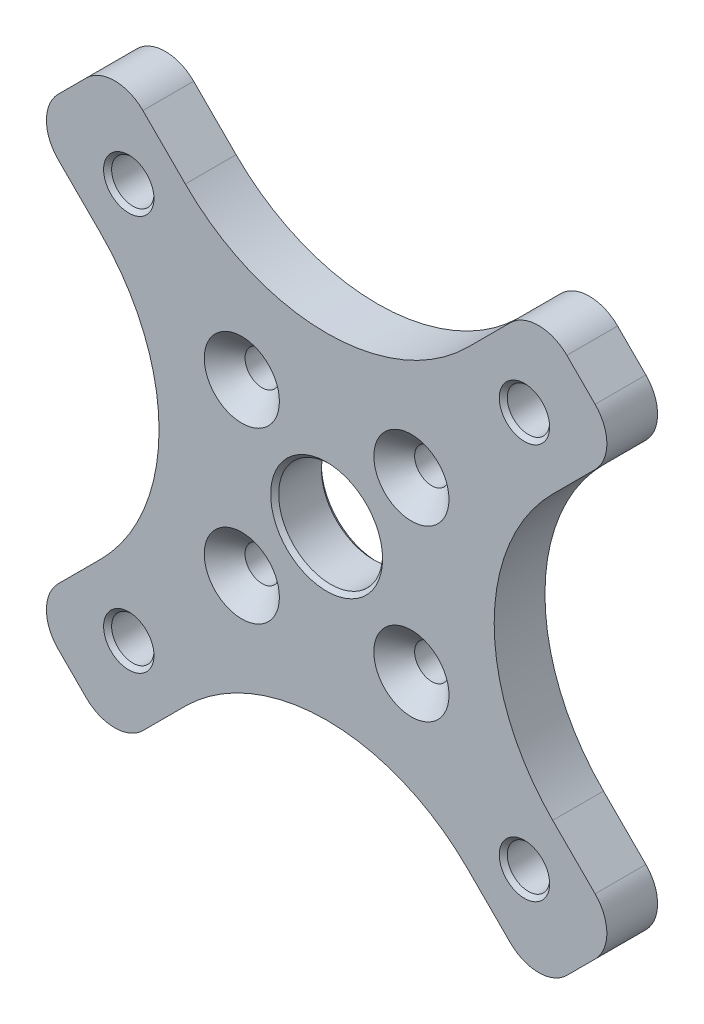
SolidWorks part; units mm, degrees
ref_plane "Front Plane" through (0, 0, 0) normal (0, 0, 1) x (1, 0, 0)
ref_plane "Top Plane" through (0, 0, 0) normal (0, 1, 0) x (1, 0, 0)
ref_plane "Right Plane" through (0, 0, 0) normal (1, 0, 0) x (0, 0, -1)
sketch "Sketch1" plane through (0, 0, 0) normal (0, 0, 1) x (1, 0, 0)
  line L0 (0, 10.6066) -> (26.5165, 37.1231)
  line L1 (26.5165, 37.1231) -> (37.1231, 26.5165)
  line L2 (37.1231, 26.5165) -> (10.6066, 0)
  line L3 (10.6066, 0) -> (37.1231, -26.5165)
  line L4 (37.1231, -26.5165) -> (26.5165, -37.1231)
  line L5 (26.5165, -37.1231) -> (0, -10.6066)
  line L6 (0, -10.6066) -> (-26.5165, -37.1231)
  line L7 (-26.5165, -37.1231) -> (-37.1231, -26.5165)
  line L8 (-37.1231, -26.5165) -> (-10.6066, 0)
  line L9 (-10.6066, 0) -> (-37.1231, 26.5165)
  line L10 (-37.1231, 26.5165) -> (-26.5165, 37.1231)
  line L11 (-26.5165, 37.1231) -> (0, 10.6066)
  line L12 (-31.8198, -31.8198) -> (31.8198, 31.8198) construction
  line L13 (-31.8198, 31.8198) -> (31.8198, -31.8198) construction
  line L14 (0, 0) -> (58.3953, 0) construction
  circle A0 centre (0, 0) radius 6.5
  dimension "D1" = 13
  dimension "D5" = 63.6396
  dimension "D2" = 45
  dimension "D3" = 15
  dimension "D4" = 90
extrude "1/4 in Sheet Metal" add sketch "Sketch1" along normal mid plane 6.35
hole_wizard "CSK for M4 Flat Head Machine Screw1" positions "Sketch5" profile "Sketch6" countersink size "M4" standard "ANSI Metric" end condition up to next
sketch "Sketch5" plane through (0, 0, 3.175) normal (0, 0, 1) x (1, 0, 0)
  line L0 (-31.8198, -31.8198) -> (31.8198, 31.8198) construction
  line L1 (-37.1231, -26.5165) -> (-26.5165, -37.1231) construction
  line L2 (37.1231, 26.5165) -> (26.5165, 37.1231) construction
  line L3 (-31.8198, 31.8198) -> (31.8198, -31.8198) construction
  line L4 (-26.5165, 37.1231) -> (-37.1231, 26.5165) construction
  line L5 (26.5165, -37.1231) -> (37.1231, -26.5165) construction
  line L7 (-10.6066, 10.6066) -> (10.6066, 10.6066) construction
  line L8 (10.6066, 10.6066) -> (10.6066, -10.6066) construction
  line L9 (10.6066, -10.6066) -> (-10.6066, -10.6066) construction
  line L10 (-10.6066, -10.6066) -> (-10.6066, 10.6066) construction
  circle A0 centre (0, 0) radius 15 construction
  point P0 (-10.6066, 10.6066)
  point P2 (10.6066, 10.6066)
  point P4 (10.6066, -10.6066)
  point P6 (-10.6066, -10.6066)
  dimension "D1" = 30
sketch "Sketch6" plane through (-10.6066, 10.6066, 3.175) normal (1, 0, 0) x (0, -1, 0)
  line L0 (0, 0) -> (0, 6.35)
  line L1 (0, 6.35) -> (2.15, 6.35)
  line L2 (2.15, 6.35) -> (2.15, 2.55)
  line L3 (2.15, 2.55) -> (4.7, 0)
  line L5 (4.7, 0) -> (0, 0)
  line L6 (-2.15, 2.55) -> (-4.7, 0) construction
  line L11 (0, -6.35) -> (0, 107.95) construction
  dimension "Thru Hole Dia." = 4.3
  dimension "Thru Hole Depth" = 6.35
  dimension "Near C'Sink Dia." = 9.4
  dimension "Near C'Sink Angle" = 90
hole_wizard "M5 Clearance Hole1" positions "Sketch7" profile "Sketch8" hole size "M5" standard "ANSI Metric" end condition up to next
sketch "Sketch7" plane through (0, 0, -3.175) normal (0, 0, -1) x (-1, 0, 0)
  line L0 (-31.8198, -31.8198) -> (31.8198, 31.8198) construction
  line L1 (-26.5165, -37.1231) -> (-37.1231, -26.5165) construction
  line L2 (26.5165, 37.1231) -> (37.1231, 26.5165) construction
  line L4 (-31.8198, 31.8198) -> (31.8198, -31.8198) construction
  line L5 (-37.1231, 26.5165) -> (-26.5165, 37.1231) construction
  line L6 (37.1231, -26.5165) -> (26.5165, -37.1231) construction
  line L8 (-24.7487, 24.7487) -> (24.7487, 24.7487) construction
  line L9 (24.7487, 24.7487) -> (24.7487, -24.7487) construction
  line L10 (24.7487, -24.7487) -> (-24.7487, -24.7487) construction
  line L11 (-24.7487, -24.7487) -> (-24.7487, 24.7487) construction
  circle A0 centre (0, 0) radius 35 construction
  point P0 (-24.7487, 24.7487)
  point P2 (24.7487, 24.7487)
  point P4 (24.7487, -24.7487)
  point P6 (-24.7487, -24.7487)
  dimension "D1" = 70
sketch "Sketch8" plane through (24.7487, 24.7487, -3.175) normal (1, 0, 0) x (0, 1, 0)
  line L0 (0, 0) -> (0, 6.35)
  line L1 (0, 6.35) -> (2.65, 6.35)
  line L2 (2.65, 6.35) -> (2.65, 0)
  line L5 (2.65, 0) -> (0, 0)
  line L11 (0, -6.35) -> (0, 107.95) construction
  dimension "Thru Hole Dia." = 5.3
  dimension "Thru Hole Depth" = 6.35
fillet "Fillet1" radius 25 4 edges at (-10.6066, 0, 0) (0, -10.6066, 0) (10.6066, 0, 0) (0, 10.6066, 0)
fillet "Fillet2" radius 5 8 edges at (26.5165, -37.1231, 0) (37.1231, -26.5165, 0) (-26.5165, -37.1231, 0) (-37.1231, -26.5165, 0) (-37.1231, 26.5165, 0) (-26.5165, 37.1231, 0) (37.1231, 26.5165, 0) (26.5165, 37.1231, 0)
chamfer "Chamfer1" distance 0.5 angle 45 10 edges at (6.5, 0, -3.175) (6.5, 0, 3.175) (27.3987, -24.7487, 3.175) (22.0987, -24.7487, -3.175) (-22.0987, -24.7487, 3.175) (-27.3987, -24.7487, -3.175) (27.3987, 24.7487, 3.175) (22.0987, 24.7487, -3.175) (-22.0987, 24.7487, 3.175) (-27.3987, 24.7487, -3.175)
